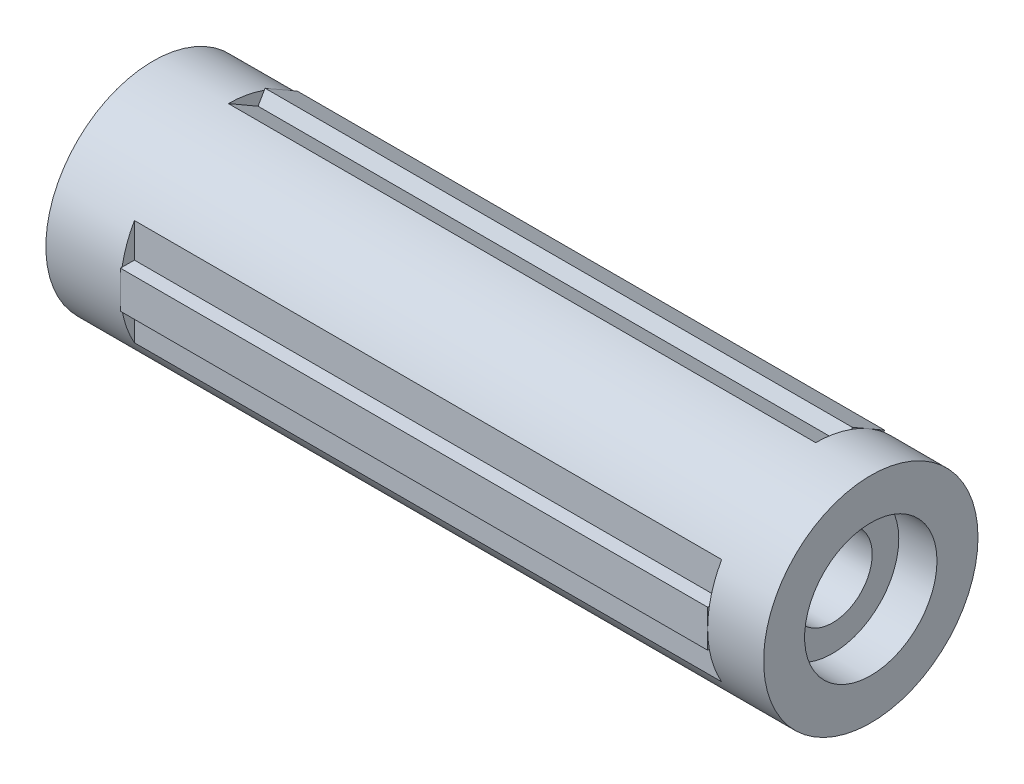
SolidWorks part; units mm, degrees
ref_plane "Ebene vorne" through (0, 0, 0) normal (0, 0, 1) x (1, 0, 0)
ref_plane "Ebene oben" through (0, 0, 0) normal (0, 1, 0) x (1, 0, 0)
ref_plane "Ebene rechts" through (0, 0, 0) normal (1, 0, 0) x (0, 0, -1)
sketch "Skizze1" plane through (0, 0, 0) normal (1, 0, 0) x (0, 0, -1)
  circle A0 centre (0, 0) radius 11.5
  dimension "D1" = 23
extrude "Aufsatz-Linear austragen1" add sketch "Skizze1" along normal blind 77
sketch "Skizze2" plane through (77, 0, 0) normal (1, 0, 0) x (0, 0, -1)
  circle A0 centre (0, 0) radius 7.1
  dimension "D1" = 14.2
extrude "Schnitt-Linear austragen1" cut sketch "Skizze2" against normal blind 4.1
sketch "Skizze3" plane through (72.9, 0, 0) normal (1, 0, 0) x (0, 0, -1)
  circle A0 centre (0, 0) radius 4.25
  dimension "D1" = 8.5
extrude "Schnitt-Linear austragen2" cut sketch "Skizze3" against normal blind 43
sketch "Skizze4" plane through (0, 0, 0) normal (-1, 0, 0) x (0, 0, 1)
  circle A0 centre (0, 0) radius 9.6
  dimension "D1" = 19.2
extrude "Schnitt-Linear austragen3" cut sketch "Skizze4" against normal blind 12.75
sketch "Skizze7" plane through (77, 0, 0) normal (1, 0, 0) x (0, 0, -1)
  line L0 (0, 13.4409) -> (0, -14.2481) construction
  line L1 (-11.5, 7.5) -> (-10, 7.5)
  line L2 (-11.5, 7.5) -> (-11.5, -7.5)
  line L3 (-11.5, -7.5) -> (-10, -7.5)
  line L4 (-10, 7.5) -> (-10, -7.5)
  dimension "D1" = 1.5
  dimension "D2" = 15
  dimension "D3" = 10
extrude "Schnitt-Linear austragen4" cut sketch "Skizze7" against normal blind 63 from offset 6 offset against normal yes
sketch "Skizze8" plane through (0, 0, 10) normal (0, 0, 1) x (1, 0, 0)
  line L0 (71, -5.6789) -> (71, 5.6789) construction
  line L1 (8, 2) -> (71, 2)
  line L2 (8, 2) -> (8, -2)
  line L3 (8, -2) -> (71, -2)
  line L4 (71, 2) -> (71, -2)
  line L5 (8, 2) -> (71, -2) construction
  line L6 (8, -2) -> (71, 2) construction
  line L7 (12.65, 0) -> (-12.65, 0) construction
  point P0 (39.5, 0)
  dimension "D1" = 31.5
  dimension "D3" = 63
  dimension "D4" = 4
extrude "Aufsatz-Linear austragen2" add sketch "Skizze8" along normal blind 1.5
sketch "Skizze10" plane through (12.75, 0, 0) normal (-1, 0, 0) x (0, 0, 1)
  line L1 (4.0389, -2.2407) -> (3.96, 2.3774)
  line L2 (3.96, 2.3774) -> (-0.0789, 4.6181)
  line L3 (-0.0789, 4.6181) -> (-4.0389, 2.2407)
  line L4 (-4.0389, 2.2407) -> (-3.96, -2.3774)
  line L5 (-3.96, -2.3774) -> (0.0789, -4.6181)
  line L6 (0.0789, -4.6181) -> (4.0389, -2.2407)
  circle A0 centre (0, 0) radius 4 construction
  dimension "D1" = 8
extrude "Schnitt-Linear austragen6" cut sketch "Skizze10" against normal blind 13.5
sketch "Skizze12" plane through (26.25, 0, 0) normal (-1, 0, 0) x (0, 0, 1)
  circle A0 centre (0, 0) radius 3
  dimension "D1" = 6
extrude "Schnitt-Linear austragen7" cut sketch "Skizze12" against normal blind 2
pattern_circular "Kreismuster3" count 3 over 360 about axis through (77, 0, 0) along (-1, 0, 0) of "Aufsatz-Linear austragen2", "Schnitt-Linear austragen4"
